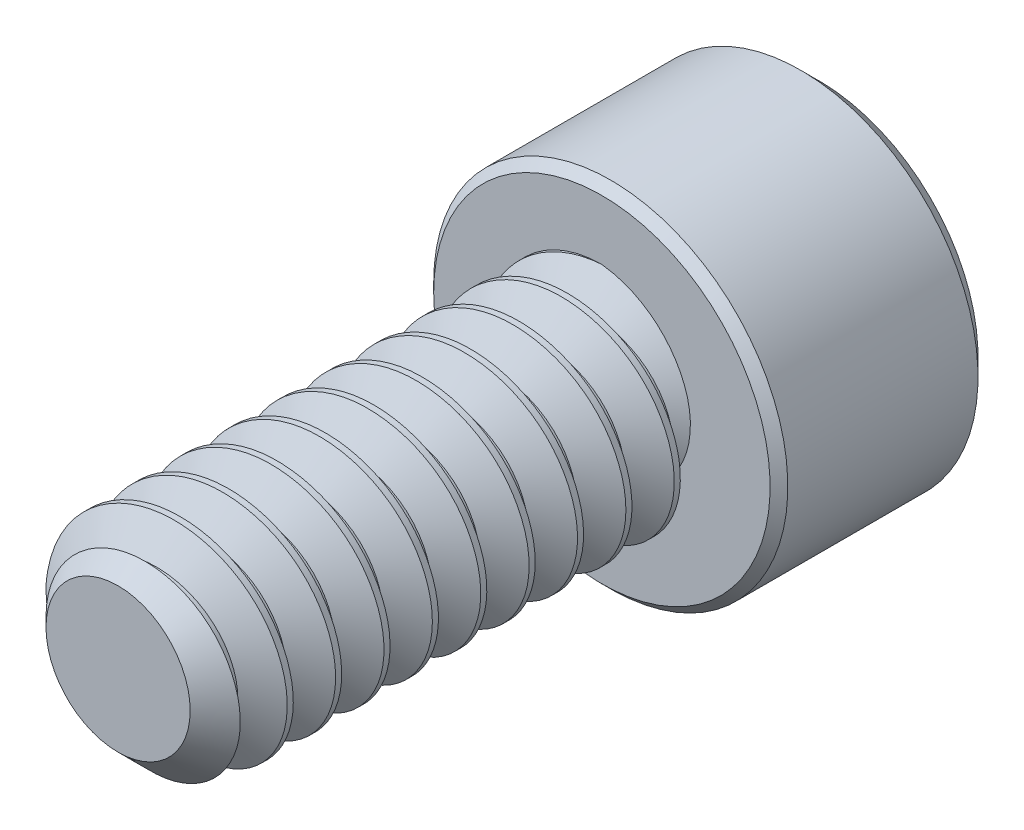
SolidWorks part; units mm, degrees
ref_plane "Front Plane" through (0, 0, 0) normal (0, 0, 1) x (1, 0, 0)
ref_plane "Top Plane" through (0, 0, 0) normal (0, 1, 0) x (1, 0, 0)
ref_plane "Right Plane" through (0, 0, 0) normal (1, 0, 0) x (0, 0, -1)
sketch "Sketch0" plane through (0, 0, 0) normal (1, 0, 0) x (0, 0, -1)
  line L0 (0, 0) -> (6.35, 0) construction
  point P2 (9.1948, 0)
  point P4 (0, 0)
  dimension "D1" = 6.35
  dimension "D2" = 2.8448
  dimension "Min Thread" = 0
sketch "Sketch1" plane through (0, 0, 0) normal (0, 0, 1) x (1, 0, 0)
  circle A0 centre (0, 0) radius 1.4224
  dimension "OD" = 2.8448
extrude "Extrude1" add sketch "Sketch1" against normal blind 6.35
sketch "Sketch2" plane through (0, 0, 0) normal (0, 0, 1) x (1, 0, 0)
  circle A0 centre (0, 0) radius 1.4224 construction
  circle A1 centre (0, 0) radius 1.4224
curve "Helix/Spiral1" pitch 0.635 height 6.985 radius 1.4224 centre (0, 0, 0) axis (0, 0, -1) start towards (0, 1, 0) parameters "pitch"=0.635
chamfer "Chamfer3" distance 0.4763 angle 45 1 edges at (1.4224, 0, 0)
sketch "Sketch3" plane through (0, 0, 0) normal (1, 0, 0) x (0, 0, -1)
  line L0 (-0.5556, 1.4224) -> (-0.3175, 1.01)
  line L1 (-0.3175, 1.01) -> (-0.2381, 1.01)
  line L2 (-0.2381, 1.01) -> (0, 1.4224)
  line L3 (-0.5556, 1.4224) -> (0, 1.4224)
  line L4 (-0.2778, 1.4224) -> (-0.2778, 1.01) construction
  line L5 (-0.4366, 1.2162) -> (-0.1191, 1.2162) construction
  line L6 (0, 1.4224) -> (0, -1.4224) construction
  dimension "D1" = 0.0794
  dimension "D2" = 0.3175
  dimension "D3" = 60
sweep "Cut-Sweep1" cut profiles "Sketch3" path "Helix/Spiral1" align with end faces yes
sketch "Sketch5" plane through (0, 0, 0) normal (1, 0, 0) x (0, 0, -1)
  line L0 (6.35, -1.0232) -> (6.35, 1.0149) construction
  line L1 (6.35, 1.4224) -> (0, 1.4224)
  line L2 (6.35, 1.4224) -> (6.35, 0)
  line L3 (6.35, 0) -> (-0.5177, 0)
  line L4 (0, 0) -> (6.35, 0) construction
  line L5 (0, 1.4224) -> (-0.5177, 0)
  line L6 (0, 0) -> (8.89, 0) construction
  dimension "D1" = 70
  dimension "D3" = 2.54
revolve "partially thread" [suppressed] add sketch "Sketch5" angle 360 about L6
sketch "Sketch6" plane through (0, 0, -6.35) normal (0, 0, -1) x (-1, 0, 0)
  circle A0 centre (0, 0) radius 2.3241
  dimension "head dia" = 4.6482
extrude "Extrude2" add sketch "Sketch6" along normal blind 2.8448
sketch "Sketch7" plane through (0, 0, -9.1948) normal (0, 0, -1) x (-1, 0, 0)
  line L1 (0, 1.3748) -> (-1.1906, 0.6874)
  line L2 (-1.1906, 0.6874) -> (-1.1906, -0.6874)
  line L3 (-1.1906, -0.6874) -> (0, -1.3748)
  line L4 (0, -1.3748) -> (1.1906, -0.6874)
  line L5 (1.1906, -0.6874) -> (1.1906, 0.6874)
  line L6 (1.1906, 0.6874) -> (0, 1.3748)
  circle A0 centre (0, 0) radius 1.1906 construction
  dimension "hex dia" = 2.3813
extrude "Cut-Extrude1" cut sketch "Sketch7" against normal blind 1.7859
sketch "Sketch8" plane through (0, 0, -9.1948) normal (0, 0, -1) x (-1, 0, 0)
  circle A0 centre (0, 0) radius 1.3748
extrude "Cut-Extrude2" cut sketch "Sketch8" against normal through all draft 45
chamfer "Chamfer1" distance 0.2324 angle 45 1 edges at (-2.3241, 0, -9.1948)
chamfer "Chamfer2" distance 0.1162 angle 45 1 edges at (-2.3241, 0, -6.35)
sketch "Sketch9" plane through (0, 0, 0) normal (1, 0, 0) x (0, 0, -1)
  line L0 (0, 1.4224) -> (0, -1.4224) construction
  line L1 (1.5875, 1.4224) -> (1.5875, -1.4224) construction
  line L2 (9.1948, 2.3241) -> (9.1948, -2.3241) construction
  line L3 (6.35, 2.3241) -> (6.35, -2.3241) construction
  line L4 (6.35, 2.2079) -> (6.35, -2.2079) construction
  line L5 (9.1948, -2.0917) -> (9.1948, 2.0917) construction
  line L6 (6.35, -2.3241) -> (6.35, 2.3241) construction
  line L7 (0, 0.9462) -> (0, -0.9462) construction
  line L8 (-0.5556, 1.4224) -> (0, 1.4224) construction
  line L9 (1.5875, 0) -> (0, 0) construction
  dimension "D1" = 1.5875
equation "\"D3@Helix/Spiral1\" = \"screw length@Extrude1\"+\"pitch@Helix/Spiral1\""
equation "\"D1@Sketch3\" = \"pitch@Helix/Spiral1\"*.125"
equation "\"D2@Sketch3\" = \"pitch@Helix/Spiral1\"*.5"
equation "\"D1@Cut-Extrude1\" = \"hex dia@Sketch7\"*.75"
equation "\"D1@Chamfer1\" = \"head dia@Sketch6\"*.05"
equation "\"D1@Sketch9\" = \"pitch@Helix/Spiral1\"*2.50"
equation "\"D1@Chamfer2\" = \"D1@Chamfer1\"/2"
equation "\"D1@Chamfer3\" = \"pitch@Helix/Spiral1\"*.750"
equation "\"D1@Sketch0\" = \"screw length@Extrude1\""
equation "\"D2@Sketch0\" = \"head depth@Extrude2\""
